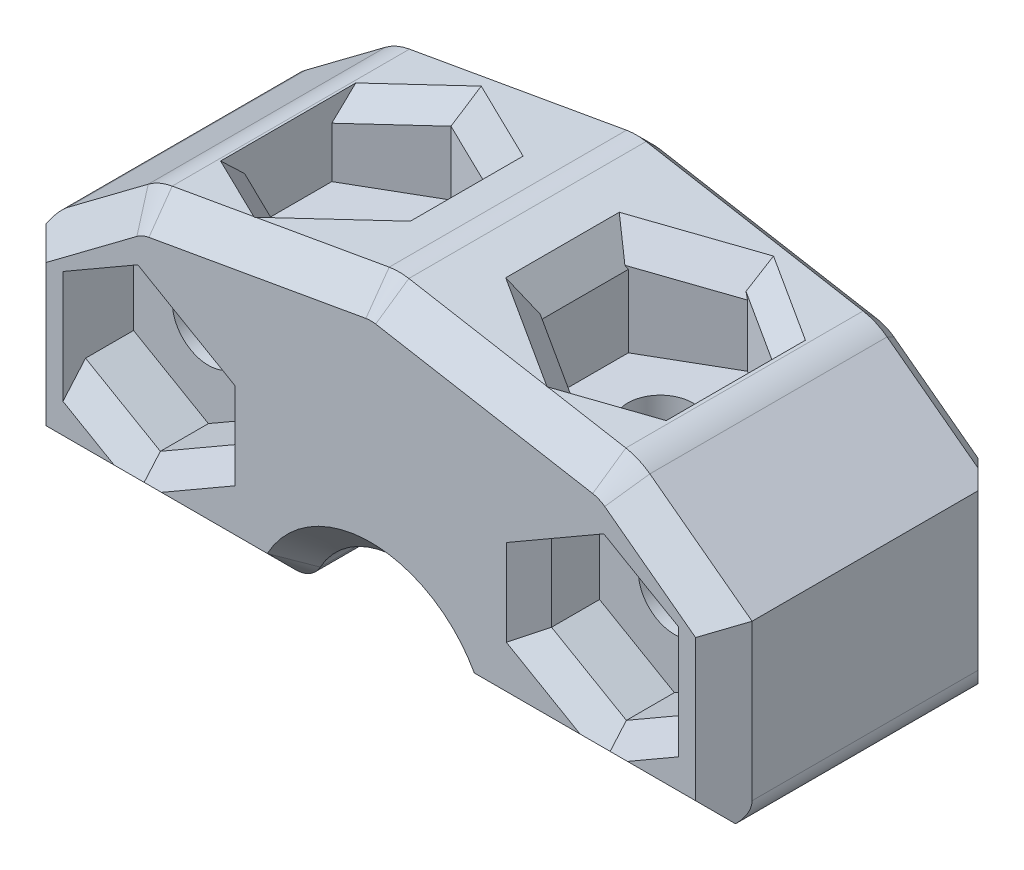
SolidWorks part; units mm, degrees
ref_plane "Front Plane" through (0, 0, 0) normal (0, 0, 1) x (1, 0, 0)
ref_plane "Top Plane" through (0, 0, 0) normal (0, 1, 0) x (1, 0, 0)
ref_plane "Right Plane" through (0, 0, 0) normal (1, 0, 0) x (0, 0, -1)
sketch "Sketch1" plane through (0, 0, 0) normal (0, 0, 1) x (1, 0, 0)
  line L0 (-3.175, 0) -> (-12.5, 0)
  line L1 (-12.5, 0) -> (-12.5, 12)
  line L2 (-12.5, 12) -> (12.5, 12)
  line L3 (0, 12) -> (0, 3.3) construction
  line L4 (12.5, 0) -> (12.5, 12)
  line L5 (3.175, 0) -> (12.5, 0)
  arc A0 (3.175, 0) -> (-3.175, 0) centre (0, 0) ccw
  dimension "D1" = 6.35
  dimension "D2" = 25
  dimension "D3" = 12
extrude "Boss-Extrude1" add sketch "Sketch1" along normal blind 10
sketch "Sketch2" plane through (0, 0, 10) normal (0, 0, 1) x (1, 0, 0)
  line L0 (0, 12) -> (-8.5, 10.5)
  line L1 (12.5, 12) -> (-12.5, 12) construction
  line L2 (-8.5, 10.5) -> (-12.5, 7.5044)
  line L3 (-12.5, 12) -> (-12.5, 0) construction
  line L4 (-12.5, 7.5044) -> (-12.5, 12)
  line L5 (-12.5, 12) -> (12.5, 12)
  line L6 (0, 8.1862) -> (0, -3.9101) construction
  line L7 (12.5, 7.5044) -> (12.5, 12)
  line L8 (8.5, 10.5) -> (12.5, 7.5044)
  line L9 (0, 12) -> (8.5, 10.5)
  line L10 (-12.5, 0) -> (-3.175, 0) construction
  line M8 (12.5, 0) -> (12.5, 12)
  line M9 (12.5, 12) -> (-12.5, 12)
  line M10 (-12.5, 12) -> (-12.5, 0)
  dimension "D1" = 10.5
  dimension "D2" = 17
  dimension "D3" = 4.4956
extrude "Cut-Extrude1" cut sketch "Sketch2" against normal through all both and the other way through all contours L2 L0 M9 M10 | L9 L8 M9 M8 region at (-9.0398, 10.7664, 10) region at (9.0398, 10.7664, 10)
chamfer "Chamfer1" distance 1 angle 45 4 edges at (-12.5, 3.7522, 0) (12.5, 3.7522, 0) (12.5, 3.7522, 10) (-12.5, 3.7522, 10)
sketch "Sketch8" plane through (0, 0, 0) normal (0, 0, -1) x (-1, 0, 0)
  line L0 (12.5, 7.5044) -> (12.5, 0) construction
  line L1 (-12.5, 0) -> (12.5, 0)
  line L2 (-12.5, 0) -> (-12.5, 1)
  line L3 (-12.5, 1) -> (12.5, 1)
  line L4 (12.5, 0) -> (12.5, 1)
  dimension "D1" = 1
extrude "Cut-Extrude6" cut sketch "Sketch8" against normal through all both and the other way through all
fillet "Fillet3" radius 1 4 edges at (-12.5, 1, 5) (-3.0134, 1, 5) (12.5, 1, 5) (3.0134, 1, 5)
sketch "Sketch4" plane through (0, 1, 0) normal (0, -1, 0) x (1, 0, 0)
  line L0 (0, 10) -> (0, 0) construction
  line L1 (-5.25, 5) -> (5.25, 5) construction
  line L2 (2.787, 10) -> (-2.787, 10) construction
  circle A0 centre (-5.25, 5) radius 1.15
  circle A1 centre (5.25, 5) radius 1.15
  point P8 (0, 5)
  point P17 (0, 5)
  dimension "D2" = 2.3
  dimension "D1" = 10.5
extrude "Cut-Extrude2" cut sketch "Sketch4" against normal through all
sketch "Sketch5" plane through (0, 0, 0) normal (0, 1, 0) x (1, 0, 0)
  line L1 (-5.25, -8.0888) -> (-2.575, -6.5444)
  line L2 (-2.575, -6.5444) -> (-2.575, -3.4556)
  line L3 (-2.575, -3.4556) -> (-5.25, -1.9112)
  line L4 (-5.25, -1.9112) -> (-7.925, -3.4556)
  line L5 (-7.925, -3.4556) -> (-7.925, -6.5444)
  line L6 (-7.925, -6.5444) -> (-5.25, -8.0888)
  line L7 (5.25, -8.0888) -> (7.925, -6.5444)
  line L8 (7.925, -6.5444) -> (7.925, -3.4556)
  line L9 (7.925, -3.4556) -> (5.25, -1.9112)
  line L10 (5.25, -1.9112) -> (2.575, -3.4556)
  line L11 (2.575, -3.4556) -> (2.575, -6.5444)
  line L12 (2.575, -6.5444) -> (5.25, -8.0888)
  circle A2 centre (-5.25, -5) radius 2.675 construction
  circle A3 centre (5.25, -5) radius 2.675 construction
  point P2 (2.2825, -4.1428)
  dimension "D1" = 5.35
extrude "Cut-Extrude3" cut sketch "Sketch5" along normal blind 8 from offset 8
fillet "Fillet2" radius 2 4 edges at (8.5, 10.5, 5) (-8.5, 10.5, 5) (0, 12, 5) (-12.5, 7.5044, 5)
chamfer "Chamfer2" distance 1 angle 45 12 edges at (0, 3.175, 10) (10.1908, 9.2337, 10) (8.4777, 10.4486, 10) (4.189, 11.2608, 10) (-10.1908, 9.2337, 10) (0, 11.9691, 10) (-8.4777, 10.4486, 10) (-4.189, 11.2608, 10) (-7.5824, 1, 10) (7.5824, 1, 10) (-3.1544, 1.14, 10) (3.1544, 1.14, 10)
sketch "Sketch6" plane through (0, 0, 10) normal (0, 0, 1) x (1, 0, 0)
  line L0 (-8.25, 5.5) -> (8.25, 5.5) construction
  circle A0 centre (-8.25, 5.5) radius 1.275
  circle A1 centre (8.25, 5.5) radius 1.275
  point P4 (0, 5.5)
  dimension "D2" = 2.55
  dimension "D1" = 16.5
  dimension "D3" = 5.5
extrude "Cut-Extrude4" cut sketch "Sketch6" against normal through all
sketch "Sketch7" plane through (0, 0, 10) normal (0, 0, 1) x (1, 0, 0)
  line L1 (-8.25, 2.44) -> (-5.6, 3.97)
  line L2 (-5.6, 3.97) -> (-5.6, 7.03)
  line L3 (-5.6, 7.03) -> (-8.25, 8.56)
  line L4 (-8.25, 8.56) -> (-10.9, 7.03)
  line L5 (-10.9, 7.03) -> (-10.9, 3.97)
  line L6 (-10.9, 3.97) -> (-8.25, 2.44)
  line L7 (8.25, 2.44) -> (10.9, 3.97)
  line L8 (10.9, 3.97) -> (10.9, 7.03)
  line L9 (10.9, 7.03) -> (8.25, 8.56)
  line L10 (8.25, 8.56) -> (5.6, 7.03)
  line L11 (5.6, 7.03) -> (5.6, 3.97)
  line L12 (5.6, 3.97) -> (8.25, 2.44)
  circle A0 centre (-8.25, 5.5) radius 2.65 construction
  circle A1 centre (8.25, 5.5) radius 2.65 construction
  dimension "D1" = 5.3
extrude "Cut-Extrude5" cut sketch "Sketch7" against normal blind 2.5
chamfer "Chamfer3" distance 0.8 angle 45 16 edges at (5.6, 5.5, 10) (9.575, 3.205, 10) (6.925, 3.205, 10) (-5.6, 5.5, 10) (-9.575, 3.205, 10) (-6.925, 3.205, 10) (3.9125, 11.3096, 7.3166) (6.5875, 10.8375, 7.3166) (6.5875, 10.8375, 2.6834) (2.575, 11.5456, 5) (3.9125, 11.3096, 2.6834) (-6.5875, 10.8375, 7.3166) (-3.9125, 11.3096, 7.3166) (-2.575, 11.5456, 5) (-3.9125, 11.3096, 2.6834) (-6.5875, 10.8375, 2.6834) first distance on face at (-8.25, 5.5, 10) first distance on face at (4.189, 11.2608, 4.5) first distance on face at (-6.5875, 9.4187, 7.3166) first distance on face at (-3.9125, 9.6548, 7.3166) first distance on face at (-2.575, 9.7728, 5) first distance on face at (-3.9125, 9.6548, 2.6834) first distance on face at (-6.5875, 9.4187, 2.6834)
chamfer "Chamfer4" distance 0.6 angle 45 12 edges at (10.1908, 9.2337, 0) (8.4777, 10.4486, 0) (4.189, 11.2608, 0) (-10.1908, 9.2337, 0) (0, 11.9691, 0) (-8.4777, 10.4486, 0) (-4.189, 11.2608, 0) (7.5824, 1, 0) (3.1544, 1.14, 0) (0, 3.175, 0) (-3.1544, 1.14, 0) (-7.5824, 1, 0)
chamfer "Chamfer5" distance 0.75 angle 45 2 edges at (9.525, 5.5, 0) (-6.975, 5.5, 0)
